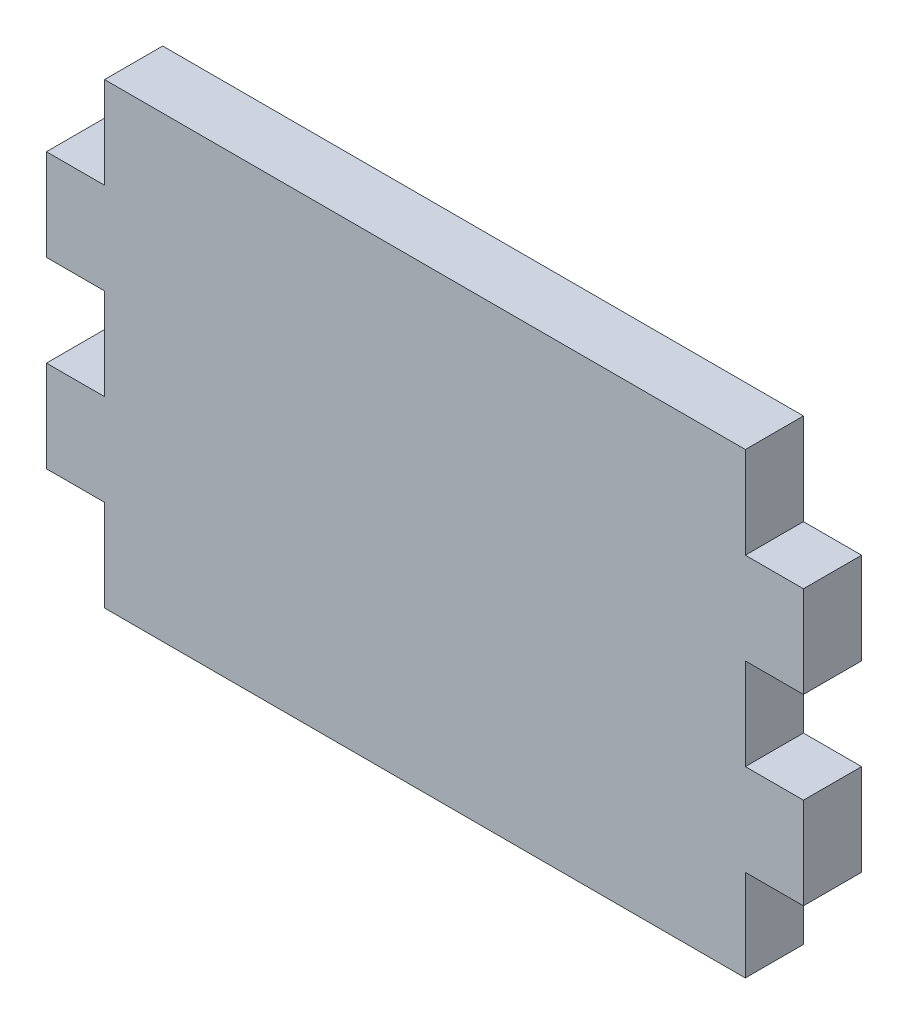
SolidWorks part; units mm, degrees
ref_plane "Front Plane" through (0, 0, 0) normal (0, 0, 1) x (1, 0, 0)
ref_plane "Top Plane" through (0, 0, 0) normal (0, 1, 0) x (1, 0, 0)
ref_plane "Right Plane" through (0, 0, 0) normal (1, 0, 0) x (0, 0, -1)
sketch "Sketch1" plane through (0, 0, 0) normal (0, 0, 1) x (1, 0, 0)
  line L0 (-70, 50) -> (-70, 40)
  line L1 (0, 0) -> (-70, 0)
  line L2 (0, 50) -> (0, 40)
  line L3 (0, 50) -> (-70, 50)
  line L4 (0, 10) -> (0, 0)
  line L5 (-70, 40) -> (-76.35, 40)
  line L6 (-76.35, 40) -> (-76.35, 30)
  line L7 (-76.35, 30) -> (-70, 30)
  line L8 (-70, 30) -> (-70, 20)
  line L9 (-70, 20) -> (-76.35, 20)
  line L10 (-76.35, 20) -> (-76.35, 10)
  line L11 (-76.35, 10) -> (-70, 10)
  line L12 (-70, 10) -> (-70, 0)
  line L13 (-35, 50) -> (-35, 0) construction
  line L14 (-70, 40) -> (-70, 30) construction
  line L15 (-70, 20) -> (-70, 10) construction
  line L16 (0, 20) -> (0, 10) construction
  line L17 (0, 40) -> (0, 30) construction
  line L18 (6.35, 10) -> (0, 10)
  line L19 (6.35, 20) -> (6.35, 10)
  line L20 (0, 20) -> (6.35, 20)
  line L21 (0, 30) -> (0, 20)
  line L22 (6.35, 30) -> (0, 30)
  line L23 (6.35, 40) -> (6.35, 30)
  line L24 (0, 40) -> (6.35, 40)
  dimension "D1" = 35
  dimension "D2" = 50
  dimension "D3" = 6.35
extrude "Body" add sketch "Sketch1" along normal blind 6.35
